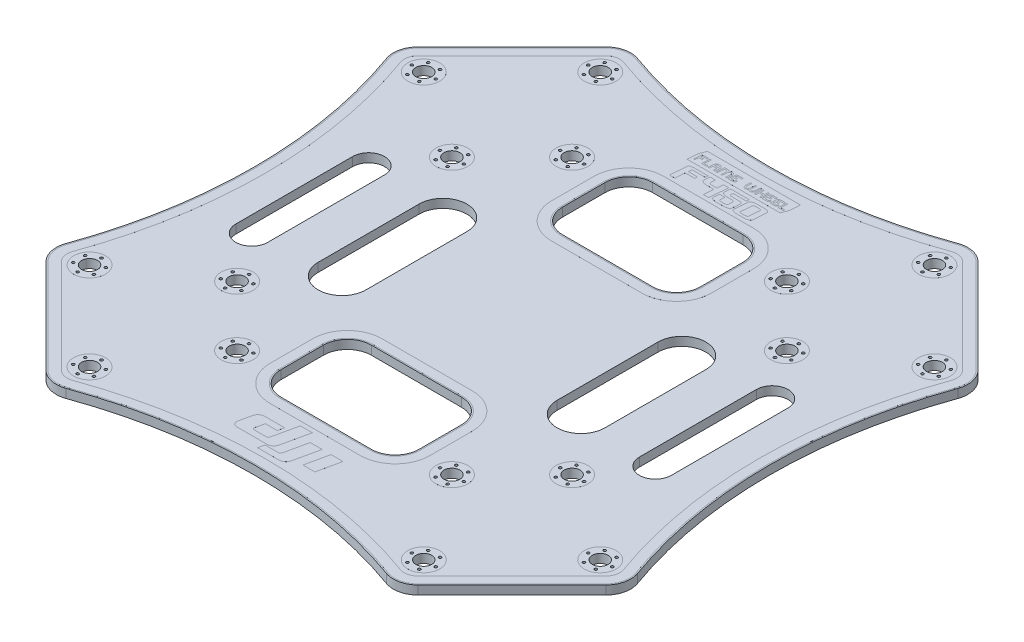
SolidWorks part; units mm, degrees
material "Mounting Plate Material"
ref_plane "Front Plane" through (0, 0, 0) normal (0, 0, 1) x (1, 0, 0)
ref_plane "Top Plane" through (0, 0, 0) normal (0, 1, 0) x (1, 0, 0)
ref_plane "Right Plane" through (0, 0, 0) normal (1, 0, 0) x (0, 0, -1)
sketch "Sketch1" plane through (0, 0, 0) normal (0, 1, 0) x (1, 0, 0)
  line L0 (-48.55, 0) -> (48.55, 0) construction
  line L1 (0, 48.55) -> (0, -48.55) construction
  line L2 (-30.1605, 53.8) -> (30.1605, 53.8) construction
  line L3 (0, 48.55) -> (0, 53.8) construction
  line L4 (-53.8, 30.1605) -> (-53.8, -30.1605) construction
  line L5 (-30.1605, -53.8) -> (30.1605, -53.8) construction
  line L6 (53.8, -30.1605) -> (53.8, 30.1605) construction
  line L7 (35.0464, 52.7056) -> (52.7056, 35.0464)
  line L8 (-52.7056, 35.0464) -> (-35.0464, 52.7056)
  line L9 (-52.7056, -35.0464) -> (-35.0464, -52.7056)
  line L10 (35.0464, -52.7056) -> (52.7056, -35.0464)
  line L11 (-43.876, -43.876) -> (43.876, 43.876) construction
  line L12 (-43.876, 43.876) -> (43.876, -43.876) construction
  line L13 (-31.7403, 54.075) -> (-31.7403, -54.075) construction
  line L14 (-31.7403, -54.075) -> (31.7403, -54.075) construction
  arc A0 (-30.1605, 53.8) -> (30.1605, 53.8) centre (0, 137.8088) ccw
  arc A1 (53.8, 30.1605) -> (53.8, -30.1605) centre (137.8088, 0) ccw
  arc A2 (30.1605, -53.8) -> (-30.1605, -53.8) centre (0, -137.8088) ccw
  arc A3 (-53.8, -30.1605) -> (-53.8, 30.1605) centre (-137.8088, 0) ccw
  arc A4 (-53.8, -30.1605) -> (-52.7056, -35.0464) centre (-49.3995, -31.7403) ccw
  arc A5 (-35.0464, -52.7056) -> (-30.1605, -53.8) centre (-31.7403, -49.3995) ccw
  arc A6 (30.1605, -53.8) -> (35.0464, -52.7056) centre (31.7403, -49.3995) ccw
  arc A7 (52.7056, -35.0464) -> (53.8, -30.1605) centre (49.3995, -31.7403) ccw
  arc A8 (53.8, 30.1605) -> (52.7056, 35.0464) centre (49.3995, 31.7403) ccw
  arc A9 (35.0464, 52.7056) -> (30.1605, 53.8) centre (31.7403, 49.3995) ccw
  arc A10 (-30.1605, 53.8) -> (-35.0464, 52.7056) centre (-31.7403, 49.3995) ccw
  arc A11 (-52.7056, 35.0464) -> (-53.8, 30.1605) centre (-49.3995, 31.7403) ccw
  point P2 (0, 0)
  point P6 (0, 0)
  point P34 (0, 0)
  dimension "D2" = 108.15
  dimension "D4" = 124.1
  dimension "D1" = 97.1
  dimension "D3" = 5.25
  dimension "D5" = 45
extrude "Boss-Extrude1" add sketch "Sketch1" along normal blind 0.825 and the other way blind 0.825
sketch "Sketch2" plane through (0, 0.825, 0) normal (0, 1, 0) x (1, 0, 0)
  line L0 (0, 18) -> (0, -18) construction
  line L1 (0, 35) -> (0, 18) construction
  line L2 (0, -18) -> (0, -35) construction
  line L3 (-13, 26.5) -> (13, 26.5) construction
  line L4 (13, 30.5) -> (13, 22.5)
  line L5 (-13, 30.5) -> (-13, 22.5)
  line L6 (-8.5, 35) -> (8.5, 35)
  line L7 (-8.5, 18) -> (8.5, 18)
  line L8 (-13, -26.5) -> (13, -26.5) construction
  line L9 (-13, -22.5) -> (-13, -30.5)
  line L10 (13, -22.5) -> (13, -30.5)
  line L11 (-8.5, -18) -> (8.5, -18)
  line L12 (-8.5, -35) -> (8.5, -35)
  line L13 (-18, 0) -> (18, 0) construction
  line L14 (-18, 0) -> (-27, 0) construction
  line L15 (18, 0) -> (27, 0) construction
  line L16 (-22.5, 9.5) -> (-22.5, -9.5) construction
  line L17 (22.5, 9.5) -> (22.5, -9.5) construction
  line L18 (-27, -9.5) -> (-27, 9.5)
  line L19 (-18, -9.5) -> (-18, 9.5)
  line L20 (18, -9.5) -> (18, 9.5)
  line L21 (27, -9.5) -> (27, 9.5)
  line L22 (-35, 0) -> (-27, 0) construction
  line L23 (-41, 0) -> (-35, 0) construction
  line L24 (27, 0) -> (35, 0) construction
  line L25 (35, 0) -> (41, 0) construction
  line L26 (-35, 11) -> (-35, -11)
  line L27 (-41, 11) -> (-41, -11)
  line L28 (-38, 11) -> (-38, -11) construction
  line L29 (35, 11) -> (35, -11)
  line L30 (41, 11) -> (41, -11)
  line L31 (38, 11) -> (38, -11) construction
  arc A0 (-8.5, 35) -> (-13, 30.5) centre (-8.5, 30.5) ccw
  arc A1 (13, 30.5) -> (8.5, 35) centre (8.5, 30.5) ccw
  arc A2 (-13, 22.5) -> (-8.5, 18) centre (-8.5, 22.5) ccw
  arc A3 (8.5, 18) -> (13, 22.5) centre (8.5, 22.5) ccw
  arc A4 (-8.5, -18) -> (-13, -22.5) centre (-8.5, -22.5) ccw
  arc A5 (13, -22.5) -> (8.5, -18) centre (8.5, -22.5) ccw
  arc A6 (8.5, -35) -> (13, -30.5) centre (8.5, -30.5) ccw
  arc A7 (-13, -30.5) -> (-8.5, -35) centre (-8.5, -30.5) ccw
  arc A8 (27, 9.5) -> (18, 9.5) centre (22.5, 9.5) ccw
  arc A9 (18, -9.5) -> (27, -9.5) centre (22.5, -9.5) ccw
  arc A10 (-27, -9.5) -> (-18, -9.5) centre (-22.5, -9.5) ccw
  arc A11 (-18, 9.5) -> (-27, 9.5) centre (-22.5, 9.5) ccw
  arc A12 (-35, 11) -> (-41, 11) centre (-38, 11) ccw
  arc A13 (-41, -11) -> (-35, -11) centre (-38, -11) ccw
  arc A14 (41, 11) -> (35, 11) centre (38, 11) ccw
  arc A15 (35, -11) -> (41, -11) centre (38, -11) ccw
  point P5 (0, 26.5)
  point P22 (0, -26.5)
  point P34 (-22.5, 0)
  point P36 (0, 0)
  point P45 (22.5, 0)
  point P64 (-38, 0)
  point P69 (38, 0)
  dimension "D6" = 26
  dimension "D8" = 36
  dimension "D13" = 8
  dimension "D18" = 22
  dimension "D1" = 36
  dimension "D2" = 17
  dimension "D3" = 17
  dimension "D4" = 26
  dimension "D5" = 8
  dimension "D7" = 8
  dimension "D9" = 9
  dimension "D10" = 9
  dimension "D11" = 19
  dimension "D12" = 19
  dimension "D14" = 8
  dimension "D15" = 6
  dimension "D16" = 6
  dimension "D17" = 22
extrude "Cut-Extrude1" cut sketch "Sketch2" against normal up to surface (1.65 mm away) up to face at (0, -0.825, 0)
sketch "Sketch3" plane through (0, 0.825, 0) normal (0, 1, 0) x (1, 0, 0)
  line L0 (-48.0833, -31.4663) -> (-31.4663, -48.0833) construction
  line L1 (-52.7056, -35.0464) -> (-35.0464, -52.7056) construction
  line L2 (-39.7748, -39.7748) -> (-43.876, -43.876) construction
  line L3 (43.876, -43.876) -> (39.7748, -39.7748) construction
  line L4 (31.4663, -48.0833) -> (48.0833, -31.4663) construction
  line L5 (43.876, 43.876) -> (39.7748, 39.7748) construction
  line L6 (31.4663, 48.0833) -> (48.0833, 31.4663) construction
  line L7 (-43.876, 43.876) -> (-39.7748, 39.7748) construction
  line L8 (-31.4663, 48.0833) -> (-48.0833, 31.4663) construction
  line L9 (-35.0464, 52.7056) -> (-52.7056, 35.0464) construction
  line L10 (52.7056, 35.0464) -> (35.0464, 52.7056) construction
  line L11 (35.0464, -52.7056) -> (52.7056, -35.0464) construction
  line L12 (-31.5403, -20.2266) -> (-20.2266, -31.5403) construction
  line L13 (31.5403, -20.2266) -> (20.2266, -31.5403) construction
  line L14 (-31.5403, 20.2266) -> (-20.2266, 31.5403) construction
  line L15 (20.2266, 31.5403) -> (31.5403, 20.2266) construction
  line L16 (-25.8834, -25.8834) -> (-39.7748, -39.7748) construction
  line L17 (-39.7748, 39.7748) -> (-25.8834, 25.8834) construction
  line L18 (39.7748, 39.7748) -> (25.8834, 25.8834) construction
  line L19 (25.8834, -25.8834) -> (39.7748, -39.7748) construction
  line L20 (-20.2266, -31.5403) -> (-31.4663, -48.0833) construction
  line L21 (-31.5403, -20.2266) -> (-48.0833, -31.4663) construction
  circle A0 centre (-48.0833, -31.4663) radius 1.5
  circle A1 centre (-31.4663, -48.0833) radius 1.5
  circle A2 centre (31.4663, -48.0833) radius 1.5
  circle A3 centre (48.0833, -31.4663) radius 1.5
  circle A4 centre (48.0833, 31.4663) radius 1.5
  circle A5 centre (31.4663, 48.0833) radius 1.5
  circle A6 centre (-31.4663, 48.0833) radius 1.5
  circle A7 centre (-48.0833, 31.4663) radius 1.5
  circle A8 centre (-31.5403, -20.2266) radius 1.5
  circle A9 centre (-20.2266, -31.5403) radius 1.5
  circle A10 centre (-31.5403, 20.2266) radius 1.5
  circle A11 centre (-20.2266, 31.5403) radius 1.5
  circle A12 centre (20.2266, 31.5403) radius 1.5
  circle A13 centre (31.5403, 20.2266) radius 1.5
  circle A14 centre (31.5403, -20.2266) radius 1.5
  circle A15 centre (20.2266, -31.5403) radius 1.5
  point P1 (-43.876, 43.876)
  dimension "D3" = 3
  dimension "D4" = 20
  dimension "D1" = 23.5
  dimension "D2" = 5.8
  dimension "D5" = 16
extrude "Cut-Extrude2" cut sketch "Sketch3" against normal up to surface (1.65 mm away) up to face at (38, -0.825, 0)
sketch "Sketch4" plane through (0, 0.825, 0) normal (0, 1, 0) x (1, 0, 0)
  line L0 (13.25, -30.5) -> (13.25, -22.5)
  line L1 (-13.25, -30.5) -> (-13.25, -22.5)
  line L2 (-8.5, -17.75) -> (8.5, -17.75)
  line L3 (-8.5, -35.25) -> (8.5, -35.25)
  line L4 (13, -30.5) -> (13, -22.5) construction
  line L5 (15.05, -30.5) -> (15.05, -22.5)
  line L6 (-8.5, -15.95) -> (8.5, -15.95)
  line L7 (-15.05, -30.5) -> (-15.05, -22.5)
  line L8 (-8.5, -37.05) -> (8.5, -37.05)
  line L9 (-8.5, 17.75) -> (8.5, 17.75)
  line L10 (-13.25, 22.5) -> (-13.25, 30.5)
  line L11 (-8.5, 35.25) -> (8.5, 35.25)
  line L12 (13.25, 30.5) -> (13.25, 22.5)
  line L13 (13, 22.5) -> (13, 30.5) construction
  line L14 (15.05, 30.5) -> (15.05, 22.5)
  line L15 (-8.5, 15.95) -> (8.5, 15.95)
  line L16 (-15.05, 22.5) -> (-15.05, 30.5)
  line L17 (-8.5, 37.05) -> (8.5, 37.05)
  line L18 (34.8696, -52.5288) -> (52.5288, -34.8696)
  line L19 (35.0464, -52.7056) -> (52.7056, -35.0464) construction
  line L20 (34.8696, 52.5288) -> (52.5288, 34.8696)
  line L21 (52.7056, 35.0464) -> (35.0464, 52.7056) construction
  line L22 (-52.5288, 34.8696) -> (-34.8696, 52.5288)
  line L23 (-35.0464, 52.7056) -> (-52.7056, 35.0464) construction
  line L24 (-52.5288, -34.8696) -> (-34.8696, -52.5288)
  line L25 (-52.7056, -35.0464) -> (-35.0464, -52.7056) construction
  line L26 (-51.256, 33.5968) -> (-33.5968, 51.256)
  line L27 (33.5968, 51.256) -> (51.256, 33.5968)
  line L28 (33.5968, -51.256) -> (51.256, -33.5968)
  line L29 (-51.256, -33.5968) -> (-33.5968, -51.256)
  line L30 (-31.4663, -45.8333) -> (-31.4663, -46.5833) construction
  line L31 (-29.5177, -46.9583) -> (-31.4663, -45.8333) construction
  line L32 (-31.4663, -45.8333) -> (-33.4148, -46.9583) construction
  line L33 (-33.4148, -46.9583) -> (-33.4148, -49.2083) construction
  line L34 (-33.4148, -49.2083) -> (-31.4663, -50.3333) construction
  line L35 (-31.4663, -50.3333) -> (-29.5177, -49.2083) construction
  line L36 (-29.5177, -49.2083) -> (-29.5177, -46.9583) construction
  line L37 (-31.4663, -45.8333) -> (-31.4663, -45.0833) construction
  line L39 (-48.0833, -29.2163) -> (-50.0318, -30.3413) construction
  line L40 (-50.0318, -30.3413) -> (-50.0318, -32.5913) construction
  line L41 (-50.0318, -32.5913) -> (-48.0833, -33.7163) construction
  line L42 (-48.0833, -33.7163) -> (-46.1347, -32.5913) construction
  line L43 (-46.1347, -32.5913) -> (-46.1347, -30.3413) construction
  line L44 (-46.1347, -30.3413) -> (-48.0833, -29.2163) construction
  line L45 (-31.5403, -17.9766) -> (-33.4888, -19.1016) construction
  line L46 (-33.4888, -19.1016) -> (-33.4888, -21.3516) construction
  line L47 (-33.4888, -21.3516) -> (-31.5403, -22.4766) construction
  line L48 (-31.5403, -22.4766) -> (-29.5917, -21.3516) construction
  line L49 (-29.5917, -21.3516) -> (-29.5917, -19.1016) construction
  line L50 (-29.5917, -19.1016) -> (-31.5403, -17.9766) construction
  line L51 (-20.2266, -29.2903) -> (-22.1751, -30.4153) construction
  line L52 (-22.1751, -30.4153) -> (-22.1751, -32.6653) construction
  line L53 (-22.1751, -32.6653) -> (-20.2266, -33.7903) construction
  line L54 (-20.2266, -33.7903) -> (-18.278, -32.6653) construction
  line L55 (-18.278, -32.6653) -> (-18.278, -30.4153) construction
  line L56 (-18.278, -30.4153) -> (-20.2266, -29.2903) construction
  line L57 (20.2266, 33.7903) -> (18.278, 32.6653) construction
  line L58 (18.278, 32.6653) -> (18.278, 30.4153) construction
  line L59 (18.278, 30.4153) -> (20.2266, 29.2903) construction
  line L60 (20.2266, 29.2903) -> (22.1751, 30.4153) construction
  line L61 (22.1751, 30.4153) -> (22.1751, 32.6653) construction
  line L62 (22.1751, 32.6653) -> (20.2266, 33.7903) construction
  line L63 (31.5403, 22.4766) -> (29.5917, 21.3516) construction
  line L64 (29.5917, 21.3516) -> (29.5917, 19.1016) construction
  line L65 (29.5917, 19.1016) -> (31.5403, 17.9766) construction
  line L66 (31.5403, 17.9766) -> (33.4888, 19.1016) construction
  line L67 (33.4888, 19.1016) -> (33.4888, 21.3516) construction
  line L68 (33.4888, 21.3516) -> (31.5403, 22.4766) construction
  line L69 (48.0833, 33.7163) -> (46.1347, 32.5913) construction
  line L70 (46.1347, 32.5913) -> (46.1347, 30.3413) construction
  line L71 (46.1347, 30.3413) -> (48.0833, 29.2163) construction
  line L72 (48.0833, 29.2163) -> (50.0318, 30.3413) construction
  line L73 (50.0318, 30.3413) -> (50.0318, 32.5913) construction
  line L74 (50.0318, 32.5913) -> (48.0833, 33.7163) construction
  line L75 (31.4663, 50.3333) -> (29.5177, 49.2083) construction
  line L76 (29.5177, 49.2083) -> (29.5177, 46.9583) construction
  line L77 (29.5177, 46.9583) -> (31.4663, 45.8333) construction
  line L78 (31.4663, 45.8333) -> (33.4148, 46.9583) construction
  line L79 (33.4148, 46.9583) -> (33.4148, 49.2083) construction
  line L80 (33.4148, 49.2083) -> (31.4663, 50.3333) construction
  line L81 (-50.3333, 31.4663) -> (-49.2083, 29.5177) construction
  line L82 (-49.2083, 29.5177) -> (-46.9583, 29.5177) construction
  line L83 (-46.9583, 29.5177) -> (-45.8333, 31.4663) construction
  line L84 (-45.8333, 31.4663) -> (-46.9583, 33.4148) construction
  line L85 (-46.9583, 33.4148) -> (-49.2083, 33.4148) construction
  line L86 (-49.2083, 33.4148) -> (-50.3333, 31.4663) construction
  line L87 (-33.7903, 20.2266) -> (-32.6653, 18.278) construction
  line L88 (-32.6653, 18.278) -> (-30.4153, 18.278) construction
  line L89 (-30.4153, 18.278) -> (-29.2903, 20.2266) construction
  line L90 (-29.2903, 20.2266) -> (-30.4153, 22.1751) construction
  line L91 (-30.4153, 22.1751) -> (-32.6653, 22.1751) construction
  line L92 (-32.6653, 22.1751) -> (-33.7903, 20.2266) construction
  line L93 (-22.4766, 31.5403) -> (-21.3516, 29.5917) construction
  line L94 (-21.3516, 29.5917) -> (-19.1016, 29.5917) construction
  line L95 (-19.1016, 29.5917) -> (-17.9766, 31.5403) construction
  line L96 (-17.9766, 31.5403) -> (-19.1016, 33.4888) construction
  line L97 (-19.1016, 33.4888) -> (-21.3516, 33.4888) construction
  line L98 (-21.3516, 33.4888) -> (-22.4766, 31.5403) construction
  line L99 (-29.2163, 48.0833) -> (-30.3413, 50.0318) construction
  line L100 (-30.3413, 50.0318) -> (-32.5913, 50.0318) construction
  line L101 (-32.5913, 50.0318) -> (-33.7163, 48.0833) construction
  line L102 (-33.7163, 48.0833) -> (-32.5913, 46.1347) construction
  line L103 (-32.5913, 46.1347) -> (-30.3413, 46.1347) construction
  line L104 (-30.3413, 46.1347) -> (-29.2163, 48.0833) construction
  line L105 (22.4766, -31.5403) -> (21.3516, -29.5917) construction
  line L106 (21.3516, -29.5917) -> (19.1016, -29.5917) construction
  line L107 (19.1016, -29.5917) -> (17.9766, -31.5403) construction
  line L108 (17.9766, -31.5403) -> (19.1016, -33.4888) construction
  line L109 (19.1016, -33.4888) -> (21.3516, -33.4888) construction
  line L110 (21.3516, -33.4888) -> (22.4766, -31.5403) construction
  line L111 (33.7903, -20.2266) -> (32.6653, -18.278) construction
  line L112 (32.6653, -18.278) -> (30.4153, -18.278) construction
  line L113 (30.4153, -18.278) -> (29.2903, -20.2266) construction
  line L114 (29.2903, -20.2266) -> (30.4153, -22.1751) construction
  line L115 (30.4153, -22.1751) -> (32.6653, -22.1751) construction
  line L116 (32.6653, -22.1751) -> (33.7903, -20.2266) construction
  line L117 (33.7163, -48.0833) -> (32.5913, -46.1347) construction
  line L118 (32.5913, -46.1347) -> (30.3413, -46.1347) construction
  line L119 (30.3413, -46.1347) -> (29.2163, -48.0833) construction
  line L120 (29.2163, -48.0833) -> (30.3413, -50.0318) construction
  line L121 (30.3413, -50.0318) -> (32.5913, -50.0318) construction
  line L122 (32.5913, -50.0318) -> (33.7163, -48.0833) construction
  line L123 (50.3333, -31.4663) -> (49.2083, -29.5177) construction
  line L124 (49.2083, -29.5177) -> (46.9583, -29.5177) construction
  line L125 (46.9583, -29.5177) -> (45.8333, -31.4663) construction
  line L126 (45.8333, -31.4663) -> (46.9583, -33.4148) construction
  line L127 (46.9583, -33.4148) -> (49.2083, -33.4148) construction
  line L128 (49.2083, -33.4148) -> (50.3333, -31.4663) construction
  arc A0 (-8.5, -17.75) -> (-13.25, -22.5) centre (-8.5, -22.5) ccw
  arc A1 (13.25, -22.5) -> (8.5, -17.75) centre (8.5, -22.5) ccw
  arc A2 (-13.25, -30.5) -> (-8.5, -35.25) centre (-8.5, -30.5) ccw
  arc A3 (8.5, -35.25) -> (13.25, -30.5) centre (8.5, -30.5) ccw
  arc A4 (8.5, -35) -> (13, -30.5) centre (8.5, -30.5) ccw construction
  arc A5 (13, -22.5) -> (8.5, -18) centre (8.5, -22.5) ccw construction
  arc A6 (-8.5, -18) -> (-13, -22.5) centre (-8.5, -22.5) ccw construction
  arc A7 (-13, -30.5) -> (-8.5, -35) centre (-8.5, -30.5) ccw construction
  arc A8 (15.05, -22.5) -> (8.5, -15.95) centre (8.5, -22.5) ccw
  arc A9 (-8.5, -15.95) -> (-15.05, -22.5) centre (-8.5, -22.5) ccw
  arc A10 (-15.05, -30.5) -> (-8.5, -37.05) centre (-8.5, -30.5) ccw
  arc A11 (8.5, -37.05) -> (15.05, -30.5) centre (8.5, -30.5) ccw
  arc A12 (-13.25, 22.5) -> (-8.5, 17.75) centre (-8.5, 22.5) ccw
  arc A13 (-8.5, 35.25) -> (-13.25, 30.5) centre (-8.5, 30.5) ccw
  arc A14 (13.25, 30.5) -> (8.5, 35.25) centre (8.5, 30.5) ccw
  arc A15 (8.5, 17.75) -> (13.25, 22.5) centre (8.5, 22.5) ccw
  arc A16 (8.5, 18) -> (13, 22.5) centre (8.5, 22.5) ccw construction
  arc A17 (13, 30.5) -> (8.5, 35) centre (8.5, 30.5) ccw construction
  arc A18 (-8.5, 35) -> (-13, 30.5) centre (-8.5, 30.5) ccw construction
  arc A19 (-13, 22.5) -> (-8.5, 18) centre (-8.5, 22.5) ccw construction
  arc A20 (8.5, 15.95) -> (15.05, 22.5) centre (8.5, 22.5) ccw
  arc A21 (-15.05, 22.5) -> (-8.5, 15.95) centre (-8.5, 22.5) ccw
  arc A22 (-8.5, 37.05) -> (-15.05, 30.5) centre (-8.5, 30.5) ccw
  arc A23 (15.05, 30.5) -> (8.5, 37.05) centre (8.5, 30.5) ccw
  arc A24 (30.245, -53.5647) -> (-30.245, -53.5647) centre (0, -137.8088) ccw
  arc A25 (30.1605, -53.8) -> (-30.1605, -53.8) centre (0, -137.8088) ccw construction
  arc A26 (-53.5647, -30.245) -> (-53.5647, 30.245) centre (-137.8088, 0) ccw
  arc A27 (-30.245, 53.5647) -> (30.245, 53.5647) centre (0, 137.8088) ccw
  arc A28 (53.5647, 30.245) -> (53.5647, -30.245) centre (137.8088, 0) ccw
  arc A29 (53.8, 30.1605) -> (53.8, -30.1605) centre (137.8088, 0) ccw construction
  arc A30 (-30.1605, 53.8) -> (30.1605, 53.8) centre (0, 137.8088) ccw construction
  arc A31 (-53.8, -30.1605) -> (-53.8, 30.1605) centre (-137.8088, 0) ccw construction
  arc A32 (34.8696, 52.5288) -> (30.245, 53.5647) centre (31.7403, 49.3995) ccw
  arc A33 (35.0464, 52.7056) -> (30.1605, 53.8) centre (31.7403, 49.3995) ccw construction
  arc A34 (53.5647, 30.245) -> (52.5288, 34.8696) centre (49.3995, 31.7403) ccw
  arc A35 (53.8, 30.1605) -> (52.7056, 35.0464) centre (49.3995, 31.7403) ccw construction
  arc A36 (52.5288, -34.8696) -> (53.5647, -30.245) centre (49.3995, -31.7403) ccw
  arc A37 (52.7056, -35.0464) -> (53.8, -30.1605) centre (49.3995, -31.7403) ccw construction
  arc A38 (30.245, -53.5647) -> (34.8696, -52.5288) centre (31.7403, -49.3995) ccw
  arc A39 (30.1605, -53.8) -> (35.0464, -52.7056) centre (31.7403, -49.3995) ccw construction
  arc A40 (-34.8696, -52.5288) -> (-30.245, -53.5647) centre (-31.7403, -49.3995) ccw
  arc A41 (-35.0464, -52.7056) -> (-30.1605, -53.8) centre (-31.7403, -49.3995) ccw construction
  arc A42 (-53.5647, -30.245) -> (-52.5288, -34.8696) centre (-49.3995, -31.7403) ccw
  arc A43 (-53.8, -30.1605) -> (-52.7056, -35.0464) centre (-49.3995, -31.7403) ccw construction
  arc A44 (-52.5288, 34.8696) -> (-53.5647, 30.245) centre (-49.3995, 31.7403) ccw
  arc A45 (-52.7056, 35.0464) -> (-53.8, 30.1605) centre (-49.3995, 31.7403) ccw construction
  arc A46 (-30.245, 53.5647) -> (-34.8696, 52.5288) centre (-31.7403, 49.3995) ccw
  arc A47 (-30.1605, 53.8) -> (-35.0464, 52.7056) centre (-31.7403, 49.3995) ccw construction
  arc A48 (-51.8706, -30.8532) -> (-51.8706, 30.8532) centre (-137.8088, 0) ccw
  arc A49 (-51.256, 33.5968) -> (-51.8706, 30.8532) centre (-49.3995, 31.7403) ccw
  arc A50 (-30.8532, 51.8706) -> (-33.5968, 51.256) centre (-31.7403, 49.3995) ccw
  arc A51 (-30.8532, 51.8706) -> (30.8532, 51.8706) centre (0, 137.8088) ccw
  arc A52 (33.5968, 51.256) -> (30.8532, 51.8706) centre (31.7403, 49.3995) ccw
  arc A53 (51.8706, 30.8532) -> (51.256, 33.5968) centre (49.3995, 31.7403) ccw
  arc A54 (51.8706, 30.8532) -> (51.8706, -30.8532) centre (137.8088, 0) ccw
  arc A55 (51.256, -33.5968) -> (51.8706, -30.8532) centre (49.3995, -31.7403) ccw
  arc A56 (30.8532, -51.8706) -> (33.5968, -51.256) centre (31.7403, -49.3995) ccw
  arc A57 (30.8532, -51.8706) -> (-30.8532, -51.8706) centre (0, -137.8088) ccw
  arc A58 (-33.5968, -51.256) -> (-30.8532, -51.8706) centre (-31.7403, -49.3995) ccw
  arc A59 (-51.8706, -30.8532) -> (-51.256, -33.5968) centre (-49.3995, -31.7403) ccw
  circle A60 centre (-31.4663, -48.0833) radius 3
  circle A61 centre (-48.0833, -31.4663) radius 3
  circle A62 centre (-31.5403, -20.2266) radius 3
  circle A63 centre (-20.2266, -31.5403) radius 3
  circle A64 centre (-48.0833, 31.4663) radius 3
  circle A65 centre (-31.5403, 20.2266) radius 3
  circle A66 centre (-20.2266, 31.5403) radius 3
  circle A67 centre (-31.4663, 48.0833) radius 3
  circle A68 centre (20.2266, 31.5403) radius 3
  circle A69 centre (31.4663, 48.0833) radius 3
  circle A70 centre (48.0833, 31.4663) radius 3
  circle A71 centre (31.5403, 20.2266) radius 3
  circle A72 centre (20.2266, -31.5403) radius 3
  circle A73 centre (31.5403, -20.2266) radius 3
  circle A74 centre (48.0833, -31.4663) radius 3
  circle A75 centre (31.4663, -48.0833) radius 3
  circle A76 centre (-31.4663, -48.0833) radius 1.5 construction
  circle A77 centre (-48.0833, -31.4663) radius 1.5 construction
  circle A78 centre (-31.5403, -20.2266) radius 1.5 construction
  circle A79 centre (-20.2266, -31.5403) radius 1.5 construction
  circle A80 centre (20.2266, -31.5403) radius 1.5 construction
  circle A81 centre (31.4663, -48.0833) radius 1.5 construction
  circle A82 centre (48.0833, -31.4663) radius 1.5 construction
  circle A83 centre (31.5403, -20.2266) radius 1.5 construction
  circle A84 centre (48.0833, 31.4663) radius 1.5 construction
  circle A85 centre (31.5403, 20.2266) radius 1.5 construction
  circle A86 centre (20.2266, 31.5403) radius 1.5 construction
  circle A87 centre (31.4663, 48.0833) radius 1.5 construction
  circle A88 centre (-20.2266, 31.5403) radius 1.5 construction
  circle A89 centre (-31.5403, 20.2266) radius 1.5 construction
  circle A90 centre (-48.0833, 31.4663) radius 1.5 construction
  circle A91 centre (-31.4663, 48.0833) radius 1.5 construction
  circle A92 centre (-48.0833, -31.4663) radius 1.5
  circle A93 centre (-31.4663, -48.0833) radius 1.5
  circle A94 centre (-20.2266, -31.5403) radius 1.5
  circle A95 centre (-31.5403, -20.2266) radius 1.5
  circle A96 centre (-48.0833, 31.4663) radius 1.5
  circle A97 centre (-31.5403, 20.2266) radius 1.5
  circle A98 centre (-20.2266, 31.5403) radius 1.5
  circle A99 centre (-31.4663, 48.0833) radius 1.5
  circle A100 centre (20.2266, 31.5403) radius 1.5
  circle A101 centre (31.4663, 48.0833) radius 1.5
  circle A102 centre (48.0833, 31.4663) radius 1.5
  circle A103 centre (31.5403, 20.2266) radius 1.5
  circle A104 centre (31.5403, -20.2266) radius 1.5
  circle A105 centre (20.2266, -31.5403) radius 1.5
  circle A106 centre (48.0833, -31.4663) radius 1.5
  circle A107 centre (31.4663, -48.0833) radius 1.5
  circle A108 centre (-31.4663, -48.0833) radius 1.9486 construction
  circle A109 centre (-48.0833, -31.4663) radius 1.9486 construction
  circle A110 centre (-31.5403, -20.2266) radius 1.9486 construction
  circle A111 centre (-20.2266, -31.5403) radius 1.9486 construction
  circle A112 centre (-31.4663, -50.3333) radius 0.25
  circle A113 centre (-29.5177, -49.2083) radius 0.25
  circle A114 centre (-29.5177, -46.9583) radius 0.25
  circle A115 centre (-31.4663, -45.8333) radius 0.25
  circle A116 centre (-33.4148, -46.9583) radius 0.25
  circle A117 centre (-33.4148, -49.2083) radius 0.25
  circle A118 centre (-48.0833, -33.7163) radius 0.25
  circle A119 centre (-46.1347, -32.5913) radius 0.25
  circle A120 centre (-46.1347, -30.3413) radius 0.25
  circle A121 centre (-48.0833, -29.2163) radius 0.25
  circle A122 centre (-50.0318, -30.3413) radius 0.25
  circle A123 centre (-50.0318, -32.5913) radius 0.25
  circle A124 centre (-31.5403, -22.4766) radius 0.25
  circle A125 centre (-29.5917, -21.3516) radius 0.25
  circle A126 centre (-29.5917, -19.1016) radius 0.25
  circle A127 centre (-31.5403, -17.9766) radius 0.25
  circle A128 centre (-33.4888, -19.1016) radius 0.25
  circle A129 centre (-33.4888, -21.3516) radius 0.25
  circle A130 centre (-20.2266, -33.7903) radius 0.25
  circle A131 centre (-18.278, -32.6653) radius 0.25
  circle A132 centre (-18.278, -30.4153) radius 0.25
  circle A133 centre (-20.2266, -29.2903) radius 0.25
  circle A134 centre (-22.1751, -30.4153) radius 0.25
  circle A135 centre (-22.1751, -32.6653) radius 0.25
  circle A136 centre (20.2266, 31.5403) radius 1.9486 construction
  circle A137 centre (31.5403, 20.2266) radius 1.9486 construction
  circle A138 centre (48.0833, 31.4663) radius 1.9486 construction
  circle A139 centre (31.4663, 48.0833) radius 1.9486 construction
  circle A140 centre (20.2266, 29.2903) radius 0.25
  circle A141 centre (22.1751, 30.4153) radius 0.25
  circle A142 centre (22.1751, 32.6653) radius 0.25
  circle A143 centre (18.278, 30.4153) radius 0.25
  circle A144 centre (18.278, 32.6653) radius 0.25
  circle A145 centre (20.2266, 33.7903) radius 0.25
  circle A146 centre (31.4663, 45.8333) radius 0.25
  circle A147 centre (29.5177, 46.9583) radius 0.25
  circle A148 centre (29.5177, 49.2083) radius 0.25
  circle A149 centre (31.4663, 50.3333) radius 0.25
  circle A150 centre (33.4148, 49.2083) radius 0.25
  circle A151 centre (33.4148, 46.9583) radius 0.25
  circle A152 centre (29.5917, 21.3516) radius 0.25
  circle A153 centre (29.5917, 19.1016) radius 0.25
  circle A154 centre (31.5403, 17.9766) radius 0.25
  circle A155 centre (33.4888, 19.1016) radius 0.25
  circle A156 centre (33.4888, 21.3516) radius 0.25
  circle A157 centre (31.5403, 22.4766) radius 0.25
  circle A158 centre (48.0833, 29.2163) radius 0.25
  circle A159 centre (46.1347, 30.3413) radius 0.25
  circle A160 centre (50.0318, 30.3413) radius 0.25
  circle A161 centre (50.0318, 32.5913) radius 0.25
  circle A162 centre (48.0833, 33.7163) radius 0.25
  circle A163 centre (46.1347, 32.5913) radius 0.25
  circle A164 centre (-48.0833, 31.4663) radius 1.9486 construction
  circle A165 centre (-31.5403, 20.2266) radius 1.9486 construction
  circle A166 centre (-20.2266, 31.5403) radius 1.9486 construction
  circle A167 centre (-31.4663, 48.0833) radius 1.9486 construction
  circle A168 centre (-46.9583, 29.5177) radius 0.25
  circle A169 centre (-45.8333, 31.4663) radius 0.25
  circle A170 centre (-46.9583, 33.4148) radius 0.25
  circle A171 centre (-49.2083, 33.4148) radius 0.25
  circle A172 centre (-50.3333, 31.4663) radius 0.25
  circle A173 centre (-49.2083, 29.5177) radius 0.25
  circle A174 centre (-32.6653, 18.278) radius 0.25
  circle A175 centre (-33.7903, 20.2266) radius 0.25
  circle A176 centre (-32.6653, 22.1751) radius 0.25
  circle A177 centre (-30.4153, 22.1751) radius 0.25
  circle A178 centre (-29.2903, 20.2266) radius 0.25
  circle A179 centre (-30.4153, 18.278) radius 0.25
  circle A180 centre (-19.1016, 29.5917) radius 0.25
  circle A181 centre (-21.3516, 29.5917) radius 0.25
  circle A182 centre (-22.4766, 31.5403) radius 0.25
  circle A183 centre (-21.3516, 33.4888) radius 0.25
  circle A184 centre (-19.1016, 33.4888) radius 0.25
  circle A185 centre (-17.9766, 31.5403) radius 0.25
  circle A186 centre (-32.5913, 46.1347) radius 0.25
  circle A187 centre (-33.7163, 48.0833) radius 0.25
  circle A188 centre (-32.5913, 50.0318) radius 0.25
  circle A189 centre (-30.3413, 50.0318) radius 0.25
  circle A190 centre (-29.2163, 48.0833) radius 0.25
  circle A191 centre (-30.3413, 46.1347) radius 0.25
  circle A192 centre (20.2266, -31.5403) radius 1.9486 construction
  circle A193 centre (31.5403, -20.2266) radius 1.9486 construction
  circle A194 centre (31.4663, -48.0833) radius 1.9486 construction
  circle A195 centre (48.0833, -31.4663) radius 1.9486 construction
  circle A196 centre (19.1016, -33.4888) radius 0.25
  circle A197 centre (21.3516, -33.4888) radius 0.25
  circle A198 centre (22.4766, -31.5403) radius 0.25
  circle A199 centre (21.3516, -29.5917) radius 0.25
  circle A200 centre (19.1016, -29.5917) radius 0.25
  circle A201 centre (17.9766, -31.5403) radius 0.25
  circle A202 centre (30.3413, -50.0318) radius 0.25
  circle A203 centre (29.2163, -48.0833) radius 0.25
  circle A204 centre (30.3413, -46.1347) radius 0.25
  circle A205 centre (32.5913, -46.1347) radius 0.25
  circle A206 centre (33.7163, -48.0833) radius 0.25
  circle A207 centre (32.5913, -50.0318) radius 0.25
  circle A208 centre (46.9583, -33.4148) radius 0.25
  circle A209 centre (45.8333, -31.4663) radius 0.25
  circle A210 centre (46.9583, -29.5177) radius 0.25
  circle A211 centre (49.2083, -29.5177) radius 0.25
  circle A212 centre (50.3333, -31.4663) radius 0.25
  circle A213 centre (49.2083, -33.4148) radius 0.25
  circle A214 centre (30.4153, -22.1751) radius 0.25
  circle A215 centre (29.2903, -20.2266) radius 0.25
  circle A216 centre (30.4153, -18.278) radius 0.25
  circle A217 centre (32.6653, -18.278) radius 0.25
  circle A218 centre (33.7903, -20.2266) radius 0.25
  circle A219 centre (32.6653, -22.1751) radius 0.25
  dimension "D1" = 0.25
  dimension "D3" = 0.25
  dimension "D5" = 0.25
  dimension "D7" = 6
  dimension "D8" = 0.5
  dimension "D2" = 1.8
  dimension "D4" = 1.8
  dimension "D6" = 1.8
extrude "Boss-Extrude2" add sketch "Sketch4" along normal blind 0.001 contours A27 A46 L22 A44 A26 A42 L24 A40 A24 A38 L18 A36 A28 A34 L20 A32 A59 A48 A49 L26 A50 A51 A52 L27 A53 A54 A55 L28 A56 A57 A58 L29 | L8 A11 L5 A8 L6 A9 L7 A10 A3 L3 A2 L1 A0 L2 A1 L0 | L14 A23 L17 A22 L16 A21 L15 A20 A15 L9 A12 L10 A13 L11 A14 L12 | A61 A92 | A60 A93 | A63 A94 | A62 A95 | A75 A107 | A72 A105 | A73 A104 | A74 A106 | A71 A103 | A70 A102 | A68 A100 | A69 A101 | A64 A96 | A65 A97 | A66 A98 | A67 A99 region at (12.8716, 0.825, 34.8716) region at (14.6824, 0.825, -26.5) region at (32.3749, 0.825, 52.2324) region at (-34.3814, 0.825, 48.0833) region at (-50.9984, 0.825, 31.4663) region at (-34.4554, 0.825, 20.2266) region at (-23.1417, 0.825, 31.5403) region at (-50.9984, 0.825, -31.4663) region at (-34.4554, 0.825, -20.2266) region at (-23.1417, 0.825, -31.5403) region at (-34.3814, 0.825, -48.0833) region at (17.3114, 0.825, -31.5403) region at (28.5511, 0.825, -48.0833) region at (45.1681, 0.825, -31.4663) region at (28.6251, 0.825, -20.2266) region at (17.3114, 0.825, 31.5403) region at (28.6251, 0.825, 20.2266) region at (45.1681, 0.825, 31.4663) region at (28.5511, 0.825, 48.0833)
mirror "Mirror2" about plane through (0, 0, 0) normal (0, 1, 0) of "Boss-Extrude2"
sketch "Sketch5" plane through (0, 0.825, 0) normal (0, 1, 0) x (1, 0, 0)
  circle A0 centre (-31.4663, -45.8333) radius 0.25
  circle A1 centre (-29.5177, -46.9583) radius 0.25
  circle A2 centre (-29.5177, -49.2083) radius 0.25
  circle A3 centre (-31.4663, -50.3333) radius 0.25
  circle A4 centre (-33.4148, -49.2083) radius 0.25
  circle A5 centre (-33.4148, -46.9583) radius 0.25
  circle A6 centre (-48.0833, -33.7163) radius 0.25
  circle A7 centre (-50.0318, -32.5913) radius 0.25
  circle A8 centre (-50.0318, -30.3413) radius 0.25
  circle A9 centre (-48.0833, -29.2163) radius 0.25
  circle A10 centre (-46.1347, -30.3413) radius 0.25
  circle A11 centre (-46.1347, -32.5913) radius 0.25
  circle A12 centre (-33.4888, -21.3516) radius 0.25
  circle A13 centre (-33.4888, -19.1016) radius 0.25
  circle A14 centre (-31.5403, -17.9766) radius 0.25
  circle A15 centre (-29.5917, -19.1016) radius 0.25
  circle A16 centre (-29.5917, -21.3516) radius 0.25
  circle A17 centre (-31.5403, -22.4766) radius 0.25
  circle A18 centre (-22.1751, -30.4153) radius 0.25
  circle A19 centre (-22.1751, -32.6653) radius 0.25
  circle A20 centre (-20.2266, -33.7903) radius 0.25
  circle A21 centre (-18.278, -32.6653) radius 0.25
  circle A22 centre (-18.278, -30.4153) radius 0.25
  circle A23 centre (-20.2266, -29.2903) radius 0.25
  circle A24 centre (-31.4663, -50.3333) radius 0.25 construction
  circle A25 centre (-33.4148, -49.2083) radius 0.25 construction
  circle A26 centre (-33.4148, -46.9583) radius 0.25 construction
  circle A27 centre (-31.4663, -45.8333) radius 0.25 construction
  circle A28 centre (-29.5177, -46.9583) radius 0.25 construction
  circle A29 centre (-29.5177, -49.2083) radius 0.25 construction
  circle A30 centre (-48.0833, -33.7163) radius 0.25 construction
  circle A31 centre (-50.0318, -32.5913) radius 0.25 construction
  circle A32 centre (-50.0318, -30.3413) radius 0.25 construction
  circle A33 centre (-48.0833, -29.2163) radius 0.25 construction
  circle A34 centre (-46.1347, -30.3413) radius 0.25 construction
  circle A35 centre (-46.1347, -32.5913) radius 0.25 construction
  circle A36 centre (-31.5403, -22.4766) radius 0.25 construction
  circle A37 centre (-33.4888, -21.3516) radius 0.25 construction
  circle A38 centre (-33.4888, -19.1016) radius 0.25 construction
  circle A39 centre (-31.5403, -17.9766) radius 0.25 construction
  circle A40 centre (-29.5917, -19.1016) radius 0.25 construction
  circle A41 centre (-29.5917, -21.3516) radius 0.25 construction
  circle A42 centre (-22.1751, -32.6653) radius 0.25 construction
  circle A43 centre (-22.1751, -30.4153) radius 0.25 construction
  circle A44 centre (-20.2266, -29.2903) radius 0.25 construction
  circle A45 centre (-18.278, -30.4153) radius 0.25 construction
  circle A46 centre (-18.278, -32.6653) radius 0.25 construction
  circle A47 centre (-20.2266, -33.7903) radius 0.25 construction
  circle A48 centre (19.1016, -33.4888) radius 0.25
  circle A49 centre (17.9766, -31.5403) radius 0.25
  circle A50 centre (19.1016, -29.5917) radius 0.25
  circle A51 centre (21.3516, -29.5917) radius 0.25
  circle A52 centre (22.4766, -31.5403) radius 0.25
  circle A53 centre (21.3516, -33.4888) radius 0.25
  circle A54 centre (19.1016, -33.4888) radius 0.25 construction
  circle A55 centre (21.3516, -33.4888) radius 0.25 construction
  circle A56 centre (17.9766, -31.5403) radius 0.25 construction
  circle A57 centre (19.1016, -29.5917) radius 0.25 construction
  circle A58 centre (21.3516, -29.5917) radius 0.25 construction
  circle A59 centre (22.4766, -31.5403) radius 0.25 construction
  circle A60 centre (29.2903, -20.2266) radius 0.25
  circle A61 centre (30.4153, -18.278) radius 0.25
  circle A62 centre (32.6653, -18.278) radius 0.25
  circle A63 centre (30.4153, -22.1751) radius 0.25
  circle A64 centre (32.6653, -22.1751) radius 0.25
  circle A65 centre (33.7903, -20.2266) radius 0.25
  circle A66 centre (29.2903, -20.2266) radius 0.25 construction
  circle A67 centre (30.4153, -18.278) radius 0.25 construction
  circle A68 centre (32.6653, -18.278) radius 0.25 construction
  circle A69 centre (30.4153, -22.1751) radius 0.25 construction
  circle A70 centre (32.6653, -22.1751) radius 0.25 construction
  circle A71 centre (33.7903, -20.2266) radius 0.25 construction
  circle A72 centre (46.9583, -29.5177) radius 0.25
  circle A73 centre (49.2083, -29.5177) radius 0.25
  circle A74 centre (45.8333, -31.4663) radius 0.25
  circle A75 centre (46.9583, -33.4148) radius 0.25
  circle A76 centre (49.2083, -33.4148) radius 0.25
  circle A77 centre (50.3333, -31.4663) radius 0.25
  circle A78 centre (45.8333, -31.4663) radius 0.25 construction
  circle A79 centre (46.9583, -29.5177) radius 0.25 construction
  circle A80 centre (49.2083, -29.5177) radius 0.25 construction
  circle A81 centre (50.3333, -31.4663) radius 0.25 construction
  circle A82 centre (49.2083, -33.4148) radius 0.25 construction
  circle A83 centre (46.9583, -33.4148) radius 0.25 construction
  circle A84 centre (30.3413, -46.1347) radius 0.25
  circle A85 centre (32.5913, -46.1347) radius 0.25
  circle A86 centre (29.2163, -48.0833) radius 0.25
  circle A87 centre (30.3413, -50.0318) radius 0.25
  circle A88 centre (32.5913, -50.0318) radius 0.25
  circle A89 centre (33.7163, -48.0833) radius 0.25
  circle A90 centre (29.2163, -48.0833) radius 0.25 construction
  circle A91 centre (30.3413, -46.1347) radius 0.25 construction
  circle A92 centre (32.5913, -46.1347) radius 0.25 construction
  circle A93 centre (30.3413, -50.0318) radius 0.25 construction
  circle A94 centre (32.5913, -50.0318) radius 0.25 construction
  circle A95 centre (33.7163, -48.0833) radius 0.25 construction
  circle A96 centre (-32.6653, 18.278) radius 0.25
  circle A97 centre (-33.7903, 20.2266) radius 0.25
  circle A98 centre (-32.6653, 22.1751) radius 0.25
  circle A99 centre (-30.4153, 22.1751) radius 0.25
  circle A100 centre (-29.2903, 20.2266) radius 0.25
  circle A101 centre (-30.4153, 18.278) radius 0.25
  circle A102 centre (-32.6653, 18.278) radius 0.25 construction
  circle A103 centre (-33.7903, 20.2266) radius 0.25 construction
  circle A104 centre (-32.6653, 22.1751) radius 0.25 construction
  circle A105 centre (-30.4153, 22.1751) radius 0.25 construction
  circle A106 centre (-29.2903, 20.2266) radius 0.25 construction
  circle A107 centre (-30.4153, 18.278) radius 0.25 construction
  circle A108 centre (-49.2083, 29.5177) radius 0.25
  circle A109 centre (-50.3333, 31.4663) radius 0.25
  circle A110 centre (-49.2083, 33.4148) radius 0.25
  circle A111 centre (-46.9583, 33.4148) radius 0.25
  circle A112 centre (-45.8333, 31.4663) radius 0.25
  circle A113 centre (-46.9583, 29.5177) radius 0.25
  circle A114 centre (-49.2083, 29.5177) radius 0.25 construction
  circle A115 centre (-50.3333, 31.4663) radius 0.25 construction
  circle A116 centre (-49.2083, 33.4148) radius 0.25 construction
  circle A117 centre (-46.9583, 33.4148) radius 0.25 construction
  circle A118 centre (-45.8333, 31.4663) radius 0.25 construction
  circle A119 centre (-46.9583, 29.5177) radius 0.25 construction
  circle A120 centre (-32.5913, 46.1347) radius 0.25
  circle A121 centre (-33.7163, 48.0833) radius 0.25
  circle A122 centre (-32.5913, 50.0318) radius 0.25
  circle A123 centre (-30.3413, 50.0318) radius 0.25
  circle A124 centre (-29.2163, 48.0833) radius 0.25
  circle A125 centre (-30.3413, 46.1347) radius 0.25
  circle A126 centre (-32.5913, 46.1347) radius 0.25 construction
  circle A127 centre (-33.7163, 48.0833) radius 0.25 construction
  circle A128 centre (-32.5913, 50.0318) radius 0.25 construction
  circle A129 centre (-30.3413, 50.0318) radius 0.25 construction
  circle A130 centre (-29.2163, 48.0833) radius 0.25 construction
  circle A131 centre (-30.3413, 46.1347) radius 0.25 construction
  circle A132 centre (-21.3516, 29.5917) radius 0.25
  circle A133 centre (-22.4766, 31.5403) radius 0.25
  circle A134 centre (-21.3516, 33.4888) radius 0.25
  circle A135 centre (-19.1016, 33.4888) radius 0.25
  circle A136 centre (-17.9766, 31.5403) radius 0.25
  circle A137 centre (-19.1016, 29.5917) radius 0.25
  circle A138 centre (-21.3516, 29.5917) radius 0.25 construction
  circle A139 centre (-22.4766, 31.5403) radius 0.25 construction
  circle A140 centre (-21.3516, 33.4888) radius 0.25 construction
  circle A141 centre (-19.1016, 33.4888) radius 0.25 construction
  circle A142 centre (-17.9766, 31.5403) radius 0.25 construction
  circle A143 centre (-19.1016, 29.5917) radius 0.25 construction
  circle A144 centre (20.2266, 29.2903) radius 0.25
  circle A145 centre (18.278, 30.4153) radius 0.25
  circle A146 centre (18.278, 32.6653) radius 0.25
  circle A147 centre (20.2266, 33.7903) radius 0.25
  circle A148 centre (22.1751, 32.6653) radius 0.25
  circle A149 centre (22.1751, 30.4153) radius 0.25
  circle A150 centre (20.2266, 29.2903) radius 0.25 construction
  circle A151 centre (18.278, 30.4153) radius 0.25 construction
  circle A152 centre (18.278, 32.6653) radius 0.25 construction
  circle A153 centre (20.2266, 33.7903) radius 0.25 construction
  circle A154 centre (22.1751, 32.6653) radius 0.25 construction
  circle A155 centre (22.1751, 30.4153) radius 0.25 construction
  circle A156 centre (29.5917, 21.3516) radius 0.25
  circle A157 centre (31.5403, 22.4766) radius 0.25
  circle A158 centre (29.5917, 19.1016) radius 0.25
  circle A159 centre (31.5403, 17.9766) radius 0.25
  circle A160 centre (33.4888, 19.1016) radius 0.25
  circle A161 centre (33.4888, 21.3516) radius 0.25
  circle A162 centre (29.5917, 21.3516) radius 0.25 construction
  circle A163 centre (29.5917, 19.1016) radius 0.25 construction
  circle A164 centre (31.5403, 22.4766) radius 0.25 construction
  circle A165 centre (31.5403, 17.9766) radius 0.25 construction
  circle A166 centre (33.4888, 19.1016) radius 0.25 construction
  circle A167 centre (33.4888, 21.3516) radius 0.25 construction
  circle A168 centre (48.0833, 29.2163) radius 0.25
  circle A169 centre (50.0318, 30.3413) radius 0.25
  circle A170 centre (50.0318, 32.5913) radius 0.25
  circle A171 centre (48.0833, 33.7163) radius 0.25
  circle A172 centre (46.1347, 32.5913) radius 0.25
  circle A173 centre (46.1347, 30.3413) radius 0.25
  circle A174 centre (46.1347, 30.3413) radius 0.25 construction
  circle A175 centre (48.0833, 29.2163) radius 0.25 construction
  circle A176 centre (50.0318, 30.3413) radius 0.25 construction
  circle A177 centre (50.0318, 32.5913) radius 0.25 construction
  circle A178 centre (48.0833, 33.7163) radius 0.25 construction
  circle A179 centre (46.1347, 32.5913) radius 0.25 construction
  circle A180 centre (31.4663, 45.8333) radius 0.25
  circle A181 centre (29.5177, 46.9583) radius 0.25
  circle A182 centre (29.5177, 49.2083) radius 0.25
  circle A183 centre (31.4663, 50.3333) radius 0.25
  circle A184 centre (33.4148, 49.2083) radius 0.25
  circle A185 centre (33.4148, 46.9583) radius 0.25
  circle A186 centre (31.4663, 45.8333) radius 0.25 construction
  circle A187 centre (29.5177, 46.9583) radius 0.25 construction
  circle A188 centre (29.5177, 49.2083) radius 0.25 construction
  circle A189 centre (31.4663, 50.3333) radius 0.25 construction
  circle A190 centre (33.4148, 49.2083) radius 0.25 construction
  circle A191 centre (33.4148, 46.9583) radius 0.25 construction
extrude "Cut-Extrude3" cut sketch "Sketch5" against normal up to surface (1.65 mm away) up to face at (-31.4663, -0.825, -45.0833)
sketch "Sketch6" plane through (0, 0.825, 0) normal (0, 1, 0) x (1, 0, 0)
  line L0 (-8.5, -37.85) -> (-2, -37.85) construction
  line L1 (-8.5, -37.85) -> (-8.5, -37.05) construction
  line L2 (-5.748, -42.85) -> (-3.448, -42.85)
  line L3 (-8.5, -37.05) -> (8.5, -37.05) construction
  line L4 (-2, -37.85) -> (0.25, -37.85)
  line L5 (0.25, -37.85) -> (-0.875, -42.978)
  line L6 (-7.8645, -44) -> (-2.1455, -44)
  line L7 (-0.875, -42.978) -> (-0.875, -37.85) construction
  line L8 (-2, -37.85) -> (-3.0217, -42.5071)
  line L9 (-0.875, -42.978) -> (-3.0217, -42.5071) construction
  line L10 (-5.6488, -40.7978) -> (-6.0238, -42.5071)
  line L11 (-8.1801, -40.6697) -> (-8.6866, -42.978)
  line L12 (-3.0217, -42.5071) -> (-6.0238, -42.5071) construction
  line L13 (-5.6488, -40.7978) -> (-3.4145, -40.7978)
  line L14 (-3.1622, -39.6478) -> (-6.9097, -39.6478)
  line L15 (-8.6866, -42.978) -> (-0.875, -42.978) construction
  line L16 (-7.8645, -44) -> (-6.9097, -39.6478) construction
  line L17 (-3.4145, -40.7978) -> (-3.1622, -39.6478)
  line L18 (1.6472, -39.6478) -> (3.8972, -39.6478)
  line L19 (-2.2097, -44.293) -> (-2.462, -45.443)
  line L20 (-2.462, -45.443) -> (1.5796, -45.443)
  line L21 (-2.2097, -44.293) -> (0.2771, -44.293)
  line L22 (1.6472, -39.6478) -> (0.7034, -43.9501)
  line L23 (3.8972, -39.6478) -> (2.85, -44.4211)
  line L24 (5.5772, -39.6478) -> (7.8272, -39.6478)
  line L25 (5.5772, -39.6478) -> (4.6224, -44)
  line L26 (7.8272, -39.6478) -> (6.8724, -44)
  line L27 (4.6224, -44) -> (6.8724, -44)
  line L28 (8.425, 42.05) -> (8.9079, 43.257)
  line L29 (8.9079, 43.257) -> (9.075, 45.25)
  line L30 (8.425, 42.05) -> (-9.075, 42.05)
  line L31 (9.075, 45.25) -> (-8.425, 45.25)
  line L32 (0, 46.5) -> (0, 45.25) construction
  line L33 (9.075, 46.5) -> (-9.075, 46.5) construction
  line L34 (-9.075, 42.05) -> (-8.9079, 44.043)
  line L35 (-8.9079, 44.043) -> (-8.425, 45.25)
  line L36 (-9.0197, 42.71) -> (8.689, 42.71) construction
  line L37 (-8.8411, 44.21) -> (8.9878, 44.21) construction
  line L38 (-0.325, 42.71) -> (-0.325, 42.05) construction
  line L39 (8.3602, 42.71) -> (8.3812, 42.96)
  line L40 (0.325, 44.21) -> (-0.325, 42.71) construction
  line L41 (0.325, 44.21) -> (0.325, 45.25) construction
  line L42 (-8.5179, 42.71) -> (-8.4122, 43.9699)
  line L43 (-8.267, 42.71) -> (-8.2083, 43.41)
  line L44 (-8.5179, 42.71) -> (-8.267, 42.71)
  line L45 (-7.8863, 44.21) -> (-7.1622, 44.21)
  line L46 (-7.1622, 44.21) -> (-7.1832, 43.96)
  line L47 (-8.1863, 43.66) -> (-7.6163, 43.66)
  line L48 (-7.8863, 43.96) -> (-7.1832, 43.96)
  line L49 (-7.8863, 44.21) -> (-7.8863, 43.96) construction
  line L50 (-7.6163, 43.66) -> (-7.6373, 43.41)
  line L51 (-7.6373, 43.41) -> (-8.2083, 43.41)
  line L52 (-6.9122, 44.21) -> (-6.6622, 44.21)
  line L53 (-6.9122, 44.21) -> (-7.023, 42.8892)
  line L54 (-6.6622, 44.21) -> (-6.7592, 43.0532)
  line L55 (-6.6736, 42.96) -> (-6.0136, 42.96)
  line L56 (-6.0345, 42.71) -> (-6.8582, 42.71)
  line L57 (-6.0136, 42.96) -> (-6.0345, 42.71)
  line L58 (-5.7845, 42.71) -> (-5.5345, 42.71)
  line L59 (-5.7845, 42.71) -> (-5.7068, 43.6372)
  line L60 (-5.5345, 42.71) -> (-5.4821, 43.335)
  line L61 (-4.7801, 42.71) -> (-4.5301, 42.71)
  line L62 (-4.7801, 42.71) -> (-4.7277, 43.335)
  line L63 (-4.5301, 42.71) -> (-4.4611, 43.5328)
  line L64 (-4.7081, 43.585) -> (-5.4611, 43.585)
  line L65 (-5.4821, 43.335) -> (-4.7277, 43.335)
  line L66 (-5.4611, 43.585) -> (-5.4585, 43.6164)
  line L67 (-4.2801, 42.71) -> (-4.1543, 44.21)
  line L68 (-4.2801, 42.71) -> (-4.0301, 42.71)
  line L69 (-2.5231, 42.71) -> (-2.2731, 42.71)
  line L70 (-2.2731, 42.71) -> (-2.1984, 43.6007)
  line L71 (-3.4016, 42.71) -> (-3.1516, 42.71)
  line L72 (-3.9493, 43.6739) -> (-3.3252, 43.6215) construction
  line L73 (-4.0301, 42.71) -> (-3.9493, 43.6739)
  line L74 (-3.4016, 42.71) -> (-3.3252, 43.6215)
  line L75 (-3.1516, 42.71) -> (-3.0708, 43.6739)
  line L76 (-3.0708, 43.6739) -> (-2.4467, 43.6215) construction
  line L77 (-4.1543, 44.21) -> (-3.6372, 44.21)
  line L78 (-2.4467, 43.6215) -> (-2.5231, 42.71)
  line L79 (-2.0231, 42.71) -> (-1.2231, 42.71)
  line L80 (-2.0231, 42.71) -> (-1.9174, 43.97)
  line L81 (-1.3934, 44.21) -> (-0.6674, 44.21)
  line L82 (-0.6674, 44.21) -> (-0.6884, 43.96)
  line L83 (-1.6934, 43.66) -> (-1.1234, 43.66)
  line L84 (-0.6884, 43.96) -> (-1.3934, 43.96)
  line L85 (-1.6934, 43.66) -> (-1.9434, 43.66) construction
  line L86 (-1.3934, 43.96) -> (-1.3934, 44.21) construction
  line L87 (-1.1234, 43.66) -> (-1.1444, 43.41)
  line L88 (-1.7144, 43.41) -> (-1.1444, 43.41)
  line L89 (-1.7144, 43.41) -> (-1.6934, 43.66) construction
  line L90 (-1.7144, 43.41) -> (-1.7521, 42.96)
  line L91 (-1.7521, 42.96) -> (-1.2021, 42.96)
  line L92 (-1.2231, 42.71) -> (-1.2021, 42.96) construction
  line L93 (5.8769, 42.71) -> (6.6769, 42.71)
  line L94 (-0.9847, 43.1774) -> (-0.7557, 43.1774)
  line L95 (7.5366, 42.71) -> (8.3602, 42.71)
  line L96 (7.3718, 42.8892) -> (7.4825, 44.21)
  line L97 (7.4825, 44.21) -> (7.7325, 44.21)
  line L98 (7.7325, 44.21) -> (7.6355, 43.0532)
  line L99 (7.7212, 42.96) -> (8.3812, 42.96)
  line L100 (6.5065, 44.21) -> (7.2325, 44.21)
  line L101 (7.2325, 44.21) -> (7.2116, 43.96)
  line L102 (6.5065, 43.96) -> (7.2116, 43.96)
  line L103 (6.2065, 43.66) -> (6.7765, 43.66)
  line L104 (6.7765, 43.66) -> (6.7556, 43.41)
  line L105 (6.1856, 43.41) -> (6.7556, 43.41)
  line L106 (6.2065, 43.66) -> (6.1856, 43.41) construction
  line L107 (6.1856, 43.41) -> (6.1478, 42.96)
  line L108 (6.1478, 42.96) -> (6.6978, 42.96)
  line L109 (6.9153, 43.1774) -> (7.1443, 43.1774)
  line L110 (5.8769, 42.71) -> (5.9825, 43.97)
  line L111 (5.9825, 43.97) -> (6.0026, 44.21) construction
  line L112 (5.7526, 44.21) -> (5.0267, 44.21)
  line L113 (5.7526, 44.21) -> (5.7317, 43.96)
  line L114 (5.7317, 43.96) -> (5.0267, 43.96)
  line L115 (5.2967, 43.66) -> (4.7267, 43.66)
  line L116 (5.2967, 43.66) -> (5.2757, 43.41)
  line L117 (5.2757, 43.41) -> (4.7057, 43.41)
  line L118 (4.7057, 43.41) -> (4.7267, 43.66) construction
  line L119 (4.7057, 43.41) -> (4.668, 42.96)
  line L120 (4.668, 42.96) -> (5.218, 42.96)
  line L121 (5.4354, 43.1774) -> (5.6644, 43.1774)
  line L122 (4.397, 42.71) -> (5.197, 42.71)
  line L123 (4.397, 42.71) -> (4.5026, 43.97)
  line L124 (4.5026, 43.97) -> (4.5228, 44.21) construction
  line L125 (4.2728, 44.21) -> (4.147, 42.71)
  line L126 (3.0184, 44.21) -> (2.8926, 42.71)
  line L127 (3.0184, 44.21) -> (3.2684, 44.21)
  line L128 (4.2728, 44.21) -> (4.0228, 44.21)
  line L129 (2.8926, 42.71) -> (3.1426, 42.71)
  line L130 (4.147, 42.71) -> (3.897, 42.71)
  line L131 (2.9555, 43.46) -> (4.2099, 43.46) construction
  line L132 (3.5722, 43.3354) -> (3.5931, 43.5846) construction
  line L133 (3.2684, 44.21) -> (3.2159, 43.5846)
  line L134 (3.2159, 43.5846) -> (3.9703, 43.5846)
  line L135 (3.9703, 43.5846) -> (4.0228, 44.21)
  line L136 (2.7684, 44.21) -> (2.6858, 43.2253)
  line L137 (3.1426, 42.71) -> (3.195, 43.3354)
  line L138 (3.195, 43.3354) -> (3.9494, 43.3354)
  line L139 (3.9494, 43.3354) -> (3.897, 42.71)
  line L140 (2.7684, 44.21) -> (2.5184, 44.21)
  line L141 (0.7614, 44.21) -> (0.6867, 43.3193)
  line L142 (0.7614, 44.21) -> (1.0114, 44.21)
  line L143 (1.6399, 44.21) -> (1.8899, 44.21)
  line L144 (1.6399, 44.21) -> (1.559, 43.2461)
  line L145 (1.8899, 44.21) -> (1.8134, 43.2985)
  line L146 (1.0114, 44.21) -> (0.9349, 43.2985)
  line L147 (2.5184, 44.21) -> (2.4376, 43.2461)
  line L148 (0.9349, 43.2985) -> (1.559, 43.2461) construction
  line L149 (1.8134, 43.2985) -> (2.4376, 43.2461) construction
  line L150 (-8.15, 37.8) -> (-7.8784, 41.0386)
  line L151 (-8.15, 37.8) -> (-7.15, 37.8)
  line L152 (-8.5, 37.05) -> (8.5, 37.05) construction
  line L153 (-6.8565, 41.3) -> (-4.3442, 41.3)
  line L154 (-6.8984, 40.8) -> (-4.3861, 40.8)
  line L155 (-4.3861, 40.8) -> (-4.3442, 41.3)
  line L156 (-6.8984, 40.8) -> (-6.8565, 41.3) construction
  line L157 (-6.8984, 40.8) -> (-6.9538, 40.14)
  line L158 (-6.9538, 40.14) -> (-5.1941, 40.14)
  line L159 (-5.1941, 40.14) -> (-5.236, 39.64)
  line L160 (-5.236, 39.64) -> (-6.9957, 39.64)
  line L161 (-6.9957, 39.64) -> (-7.15, 37.8)
  line L162 (-0.3835, 38.3) -> (1.3883, 38.3) construction
  line L163 (-3.9942, 41.3) -> (-2.9942, 41.3)
  line L164 (-3.9942, 41.3) -> (-4.0915, 40.14)
  line L165 (-2.9942, 41.3) -> (-3.0611, 40.5028)
  line L166 (-2.7274, 40.14) -> (-1.5792, 40.14)
  line L167 (-4.0915, 40.14) -> (-2.7274, 40.14) construction
  line L168 (-1.5792, 40.14) -> (-1.6211, 39.64) construction
  line L169 (-1.6211, 39.64) -> (-4.1334, 39.64) construction
  line L170 (-4.1334, 39.64) -> (-4.0915, 40.14) construction
  line L171 (-1.5792, 40.14) -> (-1.4819, 41.3)
  line L172 (-1.4819, 41.3) -> (-0.4819, 41.3)
  line L173 (-0.4819, 41.3) -> (-0.7754, 37.8)
  line L174 (-2.7693, 39.64) -> (-1.6211, 39.64)
  line L175 (-1.6211, 39.64) -> (-1.7754, 37.8)
  line L176 (-1.7754, 37.8) -> (-0.7754, 37.8)
  line L177 (-0.1319, 41.3) -> (3.3804, 41.3)
  line L178 (3.3804, 41.3) -> (3.3384, 40.8)
  line L179 (3.3384, 40.8) -> (0.8261, 40.8)
  line L180 (-0.1319, 41.3) -> (-0.2292, 40.14)
  line L181 (0.8261, 40.8) -> (0.8012, 40.5028)
  line L182 (0.8261, 40.8) -> (-0.1739, 40.8) construction
  line L183 (1.1349, 40.14) -> (2.7813, 40.14)
  line L184 (1.1349, 40.14) -> (-0.2292, 40.14) construction
  line L185 (1.0929, 39.64) -> (1.8771, 39.64)
  line L186 (3.2412, 39.64) -> (3.1288, 38.3)
  line L187 (2.2107, 39.2772) -> (2.1441, 38.4823)
  line L188 (1.8771, 39.64) -> (3.2412, 39.64) construction
  line L189 (0.6324, 38.49) -> (0.7079, 39.39)
  line L190 (0.7079, 39.39) -> (-0.2921, 39.39)
  line L191 (-0.2921, 39.39) -> (-0.3835, 38.3)
  line L192 (1.3883, 37.8) -> (1.3883, 38.3) construction
  line L193 (-8.5, 37.05) -> (-8.5, 37.8) construction
  line L194 (-8.5, 37.8) -> (-8.15, 37.8) construction
  line L195 (1.3883, 38.3) -> (3.1288, 38.3) construction
  line L196 (0.5746, 37.8) -> (2.0869, 37.8)
  line L197 (3.6884, 40.8) -> (3.4788, 38.3)
  line L198 (3.6884, 40.8) -> (3.7304, 41.3) construction
  line L199 (3.4788, 38.3) -> (3.4369, 37.8) construction
  line L200 (4.4947, 38.49) -> (4.6725, 40.61)
  line L201 (3.5836, 39.55) -> (4.5836, 39.55) construction
  line L202 (7.2007, 40.8) -> (6.9911, 38.3)
  line L203 (7.0959, 39.55) -> (6.0959, 39.55) construction
  line L204 (6.1848, 40.61) -> (6.007, 38.49)
  line L205 (3.4788, 38.3) -> (5.2349, 38.3) construction
  line L206 (5.2349, 38.3) -> (6.9911, 38.3) construction
  line L207 (4.4369, 37.8) -> (5.9491, 37.8)
  line L208 (3.4369, 37.8) -> (4.4369, 37.8) construction
  line L209 (3.6884, 40.8) -> (5.4276, 40.8) construction
  line L210 (5.4276, 40.8) -> (7.2007, 40.8) construction
  line L211 (4.7304, 41.3) -> (6.2426, 41.3)
  line L212 (3.7304, 41.3) -> (4.7304, 41.3) construction
  arc A0 (30.8532, -51.8706) -> (-30.8532, -51.8706) centre (0, -137.8088) ccw construction
  arc A1 (-2.1455, -44) -> (-0.875, -42.978) centre (-2.1455, -42.6993) ccw
  arc A2 (-3.448, -42.85) -> (-3.0217, -42.5071) centre (-3.448, -42.4136) ccw
  arc A3 (-6.0238, -42.5071) -> (-5.748, -42.85) centre (-5.748, -42.5676) ccw
  arc A4 (-8.6866, -42.978) -> (-7.8645, -44) centre (-7.8645, -43.1584) ccw
  arc A5 (-6.9097, -39.6478) -> (-8.1801, -40.6697) centre (-6.9097, -40.9484) ccw
  arc A6 (0.2771, -44.293) -> (0.7034, -43.9501) centre (0.2771, -43.8566) ccw
  arc A7 (1.5796, -45.443) -> (2.85, -44.4211) centre (1.5796, -44.1424) ccw
  arc A8 (-30.8532, 51.8706) -> (30.8532, 51.8706) centre (0, 137.8088) ccw construction
  arc A9 (-7.8863, 43.96) -> (-8.1863, 43.66) centre (-7.8863, 43.66) ccw
  arc A10 (-6.7592, 43.0532) -> (-6.6736, 42.96) centre (-6.6736, 43.046) ccw
  arc A11 (-7.023, 42.8892) -> (-6.8582, 42.71) centre (-6.8582, 42.8754) ccw
  arc A12 (-4.4611, 43.5328) -> (-5.7068, 43.6372) centre (-5.0839, 43.585) ccw
  arc A13 (-4.7081, 43.585) -> (-5.4585, 43.6164) centre (-5.0839, 43.585) ccw
  arc A14 (-3.3252, 43.6215) -> (-3.9493, 43.6739) centre (-3.6372, 43.6477) ccw
  arc A15 (-2.4467, 43.6215) -> (-3.0708, 43.6739) centre (-2.7587, 43.6477) ccw
  arc A16 (-1.3934, 43.96) -> (-1.6934, 43.66) centre (-1.3934, 43.66) ccw
  arc A17 (-2.1984, 43.6007) -> (-3.198, 43.9987) centre (-2.7587, 43.6477) ccw
  arc A18 (-3.198, 43.9987) -> (-3.6372, 44.21) centre (-3.6372, 43.6477) ccw
  arc A19 (-1.2231, 42.71) -> (-0.7557, 43.1774) centre (-1.2231, 43.1774) ccw
  arc A20 (-1.2021, 42.96) -> (-0.9847, 43.1774) centre (-1.2021, 43.1774) ccw
  arc A21 (7.3718, 42.8892) -> (7.5366, 42.71) centre (7.5366, 42.8754) ccw
  arc A22 (7.6355, 43.0532) -> (7.7212, 42.96) centre (7.7212, 43.046) ccw
  arc A23 (6.5065, 43.96) -> (6.2065, 43.66) centre (6.5065, 43.66) ccw
  arc A24 (6.6978, 42.96) -> (6.9153, 43.1774) centre (6.6978, 43.1774) ccw
  arc A25 (6.6769, 42.71) -> (7.1443, 43.1774) centre (6.6769, 43.1774) ccw
  arc A26 (5.0267, 43.96) -> (4.7267, 43.66) centre (5.0267, 43.66) ccw
  arc A27 (5.218, 42.96) -> (5.4354, 43.1774) centre (5.218, 43.1774) ccw
  arc A28 (5.197, 42.71) -> (5.6644, 43.1774) centre (5.197, 43.1774) ccw
  arc A29 (0.9349, 43.2985) -> (1.559, 43.2461) centre (1.247, 43.2723) ccw
  arc A30 (1.8134, 43.2985) -> (2.4376, 43.2461) centre (2.1255, 43.2723) ccw
  arc A31 (0.6867, 43.3193) -> (1.6862, 42.9213) centre (1.247, 43.2723) ccw
  arc A32 (1.6862, 42.9213) -> (2.6858, 43.2253) centre (2.1255, 43.2723) ccw
  arc A33 (-3.0611, 40.5028) -> (-2.7274, 40.14) centre (-2.7274, 40.4748) ccw
  arc A34 (0.8012, 40.5028) -> (1.1349, 40.14) centre (1.1349, 40.4748) ccw
  arc A35 (2.2107, 39.2772) -> (1.8771, 39.64) centre (1.8771, 39.3052) ccw
  arc A36 (3.2412, 39.64) -> (2.7813, 40.14) centre (2.7813, 39.6786) ccw
  ellipse E0 centre (-1.3934, 43.96) end of major axis (-1.9179, 43.96) minor radius 0.25 (-1.3934, 44.21) -> (-1.9174, 43.97) ccw
  ellipse E1 centre (-7.8863, 43.96) end of major axis (-7.3599, 43.96) minor radius 0.25 (-7.8863, 44.21) -> (-8.4122, 43.9699) ccw
  ellipse E2 centre (6.5065, 43.96) end of major axis (7.0309, 43.96) minor radius 0.25 (6.5065, 44.21) -> (5.9825, 43.97) ccw
  ellipse E3 centre (5.0267, 43.96) end of major axis (5.5511, 43.96) minor radius 0.25 (5.0267, 44.21) -> (4.5026, 43.97) ccw
  ellipse E4 centre (-6.8784, 41.0386) end of major axis (-7.8787, 41.0325) minor radius 0.2613 (-6.8565, 41.3) -> (-7.8784, 41.0386) ccw
  ellipse E5 centre (-2.7274, 40.14) end of major axis (-1.3627, 40.1577) minor radius 0.4997 (-4.0915, 40.14) -> (-2.7693, 39.64) ccw
  ellipse E6 centre (1.1349, 40.14) end of major axis (2.4996, 40.1577) minor radius 0.4997 (-0.2292, 40.14) -> (1.0929, 39.64) ccw
  ellipse E7 centre (0.6165, 38.3) end of major axis (-0.3843, 38.2721) minor radius 0.4994 (-0.3835, 38.3) -> (0.5746, 37.8) ccw
  ellipse E8 centre (5.2509, 38.49) end of major axis (4.4946, 38.4857) minor radius 0.19 (4.4947, 38.49) -> (6.007, 38.49) ccw
  ellipse E9 centre (1.3883, 38.4862) end of major axis (2.1442, 38.4862) minor radius 0.1862 (0.6324, 38.49) -> (2.1441, 38.4823) ccw
  ellipse E10 centre (2.1288, 38.3) end of major axis (3.1296, 38.3279) minor radius 0.4994 (2.0869, 37.8) -> (3.1288, 38.3) ccw
  ellipse E11 centre (4.4788, 38.3) end of major axis (5.4796, 38.3279) minor radius 0.4994 (3.4788, 38.3) -> (4.4369, 37.8) ccw
  ellipse E12 centre (5.4286, 40.61) end of major axis (6.185, 40.6143) minor radius 0.19 (6.1848, 40.61) -> (4.6725, 40.61) ccw
  ellipse E13 centre (5.9911, 38.3) end of major axis (6.9919, 38.3279) minor radius 0.4994 (5.9491, 37.8) -> (6.9911, 38.3) ccw
  ellipse E14 centre (4.6884, 40.8) end of major axis (3.6877, 40.7721) minor radius 0.4994 (4.7304, 41.3) -> (3.6884, 40.8) ccw
  ellipse E15 centre (6.2007, 40.8) end of major axis (7.2015, 40.8279) minor radius 0.4994 (7.2007, 40.8) -> (6.2426, 41.3) ccw
  point P17 (0, -46.5)
  point P57 (0, 46.5)
  point P61 (0, 43.46)
  point P216 (3.5827, 43.46)
  dimension "D7" = 2.3
  dimension "D10" = 1.75
  dimension "D12" = 1.75
  dimension "D16" = 1.3
  dimension "D23" = 0.5
  dimension "D26" = 0.25
  dimension "D31" = 0.25
  dimension "D33" = 1
  dimension "D38" = 0.25
  dimension "D44" = 0.25
  dimension "D48" = 0.3
  dimension "D51" = 0.25
  dimension "D52" = 0.5
  dimension "D53" = 0.25
  dimension "D54" = 0.25
  dimension "D55" = 0.25
  dimension "D61" = 3.25
  dimension "D72" = 3.5
  dimension "D75" = 0.25
  dimension "D77" = 0.5
  dimension "D1" = 6.5
  dimension "D2" = 0.8
  dimension "D3" = 2.25
  dimension "D4" = 2.5
  dimension "D5" = 5.25
  dimension "D6" = 1.15
  dimension "D8" = 0.75
  dimension "D9" = 2.5
  dimension "D11" = 1.15
  dimension "D13" = 1.68
  dimension "D14" = 0.3
  dimension "D15" = 1.15
  dimension "D17" = 2
  dimension "D18" = 3.2
  dimension "D19" = 1.25
  dimension "D20" = 0.65
  dimension "D21" = 17.5
  dimension "D22" = 1.5
  dimension "D24" = 0.25
  dimension "D25" = 1.25
  dimension "D27" = 0.3
  dimension "D28" = 0.57
  dimension "D29" = 0.25
  dimension "D30" = 0.25
  dimension "D32" = 0.66
  dimension "D34" = 0.25
  dimension "D35" = 0.25
  dimension "D36" = 0.25
  dimension "D37" = 1.25
  dimension "D39" = 0.25
  dimension "D40" = 0.25
  dimension "D41" = 0.25
  dimension "D42" = 2
  dimension "D43" = 0.25
  dimension "D45" = 0.8
  dimension "D46" = 1.25
  dimension "D47" = 0.57
  dimension "D49" = 0.25
  dimension "D50" = 0.25
  dimension "D56" = 1.25
  dimension "D57" = 0.25
  dimension "D58" = 0.25
  dimension "D59" = 0.25
  dimension "D60" = 2
  dimension "D62" = 1
  dimension "D63" = 0.75
  dimension "D64" = 0.66
  dimension "D65" = 0.75
  dimension "D66" = 3.5
  dimension "D67" = 0.5
  dimension "D68" = 0.66
  dimension "D69" = 2.75
  dimension "D70" = 0.35
  dimension "D71" = 0.8
  dimension "D73" = 0.35
  dimension "D74" = 3.5
  dimension "D76" = 0.9
  dimension "D78" = 0.35
  dimension "D79" = 0.35
  dimension "D80" = 3.5
extrude "Boss-Extrude3" add sketch "Sketch6" along normal blind 0.001 contours L14 A5 L11 A4 L6 A1 L5 L4 L8 A2 L2 A3 L10 L13 L17 | L20 A7 L23 L18 L22 A6 L21 L19 | L25 L27 L26 L24 | L35 L34 L30 L28 L29 L31 E1 L45 L46 L48 A9 L47 L50 L51 L43 L44 L42 A12 L63 L61 L62 L65 L60 L58 L59 A11 L53 L52 L54 A10 L55 L57 L56 | L64 A13 L66 | L153 E4 L150 L151 L161 L160 L159 L158 L157 L154 L155 | L164 E5 L174 L175 L176 L173 L172 L171 L166 A33 L165 L163 | E9 L189 L190 L191 L186 A36 L183 A34 L181 L179 L178 L177 L180 E6 L185 A35 L187 | L202 E15 L211 E14 L197 E11 L207 E13 E12 L204 E8 L200 region at (-4.598, 0.825, 42.9586) region at (1.5115, 0.825, 42.9827) region at (6.2248, 0.825, 41.8239) region at (0.0124, 0.825, -43.6883) region at (-5.084, 0.825, -43.7445) region at (-6.8562, 0.825, -39.9243) region at (-1.9273, 0.825, -39.856) region at (1.6242, 0.825, -41.2486) region at (4.1392, 0.825, -41.1519)
sketch3d "3DSketch1"
  line L0 (-48.0833, 0.826, -31.4663) -> (-48.0833, -0.826, -31.4663) construction
  line L1 (-48.0833, -0.826, -31.4663) -> (-48.0833, 0.826, -31.4663) construction
  line L2 (-48.0833, 0.826, -31.4663) -> (-48.0833, 0.825, -31.4663) construction
  line L3 (-31.4663, 0.826, -48.0833) -> (-31.4663, -0.826, -48.0833) construction
  line L4 (-31.4663, -0.826, -48.0833) -> (-31.4663, 0.826, -48.0833) construction
  line L5 (-31.4663, -0.826, -48.0833) -> (-31.4663, -0.825, -48.0833) construction
  line L6 (-20.2266, 0.826, -31.5403) -> (-20.2266, -0.826, -31.5403) construction
  line L7 (-20.2266, -0.826, -31.5403) -> (-20.2266, 0.826, -31.5403) construction
  line L8 (-20.2266, 0.826, -31.5403) -> (-20.2266, 0.825, -31.5403) construction
  line L9 (-20.2266, -0.826, -31.5403) -> (-20.2266, -0.825, -31.5403) construction
  line L10 (-31.5403, -0.826, -20.2266) -> (-31.5403, 0.826, -20.2266) construction
  line L11 (-31.5403, -0.826, -20.2266) -> (-31.5403, 0.826, -20.2266) construction
  line L12 (-31.5403, -0.826, -20.2266) -> (-31.5403, -0.825, -20.2266) construction
  line L13 (-31.5403, 0.826, -20.2266) -> (-31.5403, 0.825, -20.2266) construction
  line L14 (31.5403, 0.826, -20.2266) -> (31.5403, -0.826, -20.2266) construction
  line L15 (31.5403, -0.826, -20.2266) -> (31.5403, 0.826, -20.2266) construction
  line L16 (31.5403, 0.826, -20.2266) -> (31.5403, 0.825, -20.2266) construction
  line L17 (31.5403, -0.826, -20.2266) -> (31.5403, -0.825, -20.2266) construction
  line L18 (20.2266, 0.826, -31.5403) -> (20.2266, -0.826, -31.5403) construction
  line L19 (20.2266, -0.826, -31.5403) -> (20.2266, 0.826, -31.5403) construction
  line L20 (20.2266, 0.826, -31.5403) -> (20.2266, 0.825, -31.5403) construction
  line L21 (20.2266, -0.826, -31.5403) -> (20.2266, -0.825, -31.5403) construction
  line L22 (31.4663, 0.826, -48.0833) -> (31.4663, -0.826, -48.0833) construction
  line L23 (31.4663, -0.826, -48.0833) -> (31.4663, 0.826, -48.0833) construction
  line L24 (31.4663, 0.826, -48.0833) -> (31.4663, 0.825, -48.0833) construction
  line L25 (31.4663, -0.826, -48.0833) -> (31.4663, -0.825, -48.0833) construction
  line L26 (48.0833, 0.826, -31.4663) -> (48.0833, -0.826, -31.4663) construction
  line L27 (48.0833, -0.826, -31.4663) -> (48.0833, 0.826, -31.4663) construction
  line L28 (48.0833, 0.826, -31.4663) -> (48.0833, 0.825, -31.4663) construction
  line L29 (48.0833, -0.826, -31.4663) -> (48.0833, -0.825, -31.4663) construction
  line L30 (31.5403, 0.826, 20.2266) -> (31.5403, -0.826, 20.2266) construction
  line L31 (31.5403, -0.826, 20.2266) -> (31.5403, 0.826, 20.2266) construction
  line L32 (31.5403, 0.826, 20.2266) -> (31.5403, 0.825, 20.2266) construction
  line L33 (31.5403, -0.826, 20.2266) -> (31.5403, -0.825, 20.2266) construction
  line L34 (20.2266, 0.826, 31.5403) -> (20.2266, -0.826, 31.5403) construction
  line L35 (20.2266, -0.826, 31.5403) -> (20.2266, 0.826, 31.5403) construction
  line L36 (48.0833, 0.826, 31.4663) -> (48.0833, -0.826, 31.4663) construction
  line L37 (48.0833, -0.826, 31.4663) -> (48.0833, 0.826, 31.4663) construction
  line L38 (48.0833, 0.826, 31.4663) -> (48.0833, 0.825, 31.4663) construction
  line L39 (48.0833, -0.826, 31.4663) -> (48.0833, -0.825, 31.4663) construction
  line L40 (31.4663, 0.826, 48.0833) -> (31.4663, -0.826, 48.0833) construction
  line L41 (31.4663, -0.826, 48.0833) -> (31.4663, 0.826, 48.0833) construction
  line L42 (-31.4663, 0.826, 48.0833) -> (-31.4663, -0.826, 48.0833) construction
  line L43 (-31.4663, -0.826, 48.0833) -> (-31.4663, 0.826, 48.0833) construction
  line L44 (-48.0833, 0.826, 31.4663) -> (-48.0833, -0.826, 31.4663) construction
  line L45 (-48.0833, -0.826, 31.4663) -> (-48.0833, 0.826, 31.4663) construction
  line L46 (-20.2266, 0.826, 31.5403) -> (-20.2266, -0.826, 31.5403) construction
  line L47 (-20.2266, -0.826, 31.5403) -> (-20.2266, 0.826, 31.5403) construction
  line L48 (-20.2266, 0.826, 31.5403) -> (-20.2266, 0.825, 31.5403) construction
  line L49 (-31.5403, 0.826, 20.2266) -> (-31.5403, -0.826, 20.2266) construction
  line L50 (-31.5403, -0.826, 20.2266) -> (-31.5403, 0.826, 20.2266) construction
  line L51 (-31.5403, 0.826, 20.2266) -> (-31.5403, 0.825, 20.2266) construction
  point P98 (0, 0, 0)
  point P99 (0, 0, 0)
  point P100 (-31.5403, 0.826, 20.2266)
